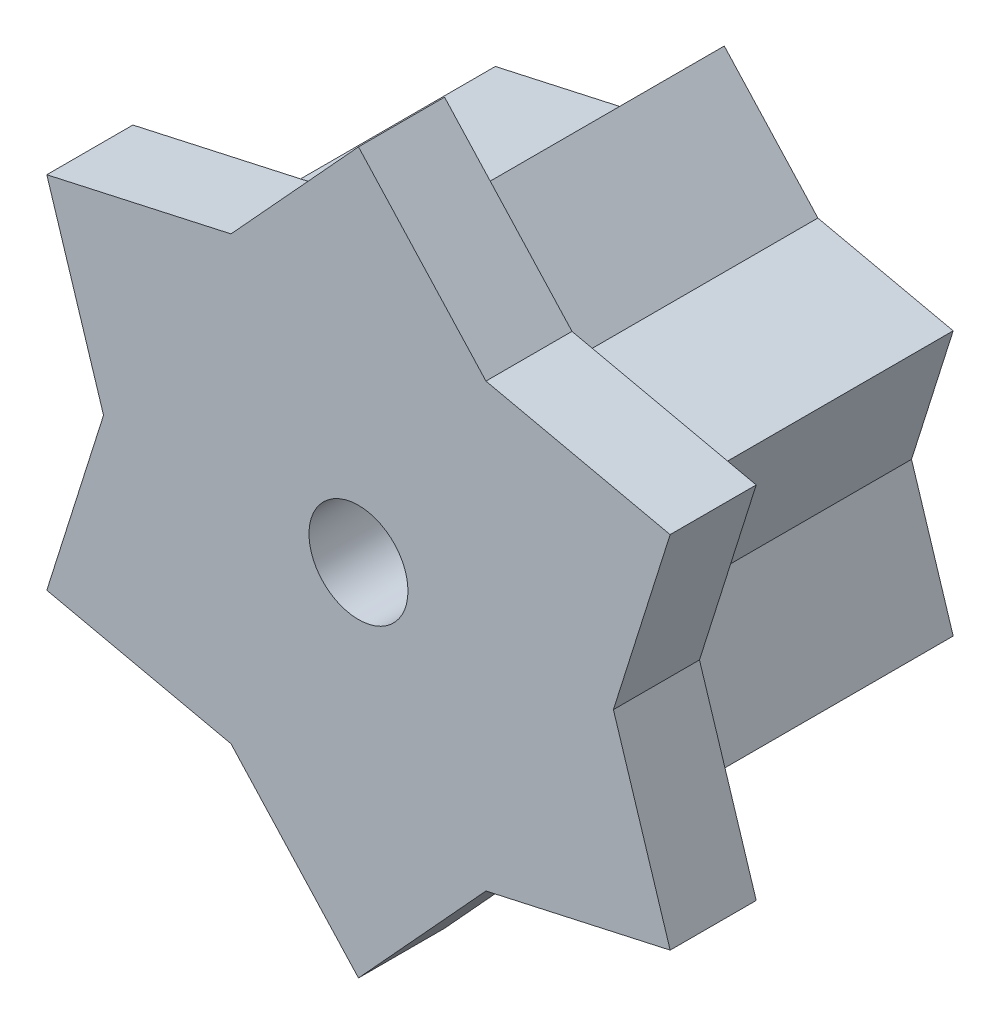
SolidWorks part; units mm, degrees
ref_plane "Front Plane" through (0, 0, 0) normal (0, 0, 1) x (1, 0, 0)
ref_plane "Top Plane" through (0, 0, 0) normal (0, 1, 0) x (1, 0, 0)
ref_plane "Right Plane" through (0, 0, 0) normal (1, 0, 0) x (0, 0, -1)
sketch "Sketch1" plane through (0, 0, 0) normal (0, 0, 1) x (1, 0, 0)
  line L0 (0, 6.1428) -> (0, -5.749) construction
  line L1 (-3.0597, 2.8037) -> (0, 6.1428)
  line L2 (0, 6.1428) -> (3.0597, 2.8037)
  line L3 (0.8982, 4.0516) -> (5.3198, 3.0714)
  line L4 (5.3198, 3.0714) -> (3.9579, -1.2479)
  line L5 (3.9579, 1.2479) -> (5.3198, -3.0714)
  line L6 (5.3198, -3.0714) -> (0.8982, -4.0516)
  line L7 (3.0597, -2.8037) -> (0, -6.1428)
  line L8 (0, -6.1428) -> (-3.0597, -2.8037)
  line L9 (-0.8982, -4.0516) -> (-5.3198, -3.0714)
  line L10 (-5.3198, -3.0714) -> (-3.9579, 1.2479)
  line L11 (-3.9579, -1.2479) -> (-5.3198, 3.0714)
  line L12 (-5.3198, 3.0714) -> (-0.8982, 4.0516)
  circle A0 centre (0, 0) radius 1.15
  circle A1 centre (0, 0) radius 4.15
  point P26 (0, 0)
  dimension "D1" = 2.3
  dimension "D3" = 85
  dimension "D4" = 42.5
  dimension "D2" = 3
  dimension "D5" = 6
extrude "Boss-Extrude1" add sketch "Sketch1" against normal blind 6.5 contours A1 A0 | A1 L1 L12 L11 L10 | L2 L0 A1 L3 | L0 L1 L12 A1 | A1 L12 L1 | A1 L2 L3 | A1 L5 L4 L3 L2 | L0 A1 A0 | A1 L11 L10 L9 L8 | A1 L10 L11 | A1 L8 L9 | A1 L9 L8 L7 L6 | A1 L6 L7 | A1 L7 L6 L5 L4 | A1 L4 L5 | A0 L0 | L0 A0 region at (0.718, 4.7126, 0) region at (-0.718, 4.7126, 0) region at (1.8672, 0, 0) region at (-1.8672, 0, 0) region at (-2.0957, 3.6299, 0) region at (-4.0813, 2.3563, 0) region at (4.0813, 2.3563, 0) region at (2.0957, 3.6299, 0) region at (0.4881, 0, 0) region at (-0.4881, 0, 0) region at (-4.1915, 0, 0) region at (-4.0813, -2.3563, 0) region at (4.1915, 0, 0) region at (4.0813, -2.3563, 0) region at (0.4572, -4.1746, 0) region at (-2.0957, -3.6299, 0) region at (2.0957, -3.6299, 0)
sketch "Sketch2" plane through (0, 0, 0) normal (0, 0, 1) x (1, 0, 0)
  line L0 (2.9621, 5.1305) -> (0, 8.3631)
  line L1 (0, 8.3631) -> (-2.9621, 5.1305)
  line L2 (-2.9621, 5.1305) -> (-7.2426, 4.1815)
  line L3 (-7.2426, 4.1815) -> (-5.9242, 0)
  line L4 (-5.9242, 0) -> (-7.2426, -4.1815)
  line L5 (-7.2426, -4.1815) -> (-2.9621, -5.1305)
  line L6 (-2.9621, -5.1305) -> (0, -8.3631)
  line L7 (0, -8.3631) -> (2.9621, -5.1305)
  line L8 (2.9621, -5.1305) -> (7.2426, -4.1815)
  line L9 (7.2426, -4.1815) -> (5.9242, 0)
  line L10 (5.9242, 0) -> (7.2426, 4.1815)
  line L11 (7.2426, 4.1815) -> (2.9621, 5.1305)
  line L12 (5.3198, -3.0714) -> (4.3514, 0)
  line L13 (4.3514, 0) -> (5.3198, 3.0714)
  line L14 (5.3198, 3.0714) -> (2.1757, 3.7684)
  line L15 (2.1757, 3.7684) -> (0, 6.1428)
  line L16 (0, 6.1428) -> (-2.1757, 3.7684)
  line L17 (-2.1757, 3.7684) -> (-5.3198, 3.0714)
  line L18 (-5.3198, 3.0714) -> (-4.3514, 0)
  line L19 (-4.3514, 0) -> (-5.3198, -3.0714)
  line L20 (-5.3198, -3.0714) -> (-2.1757, -3.7684)
  line L21 (-2.1757, -3.7684) -> (0, -6.1428)
  line L22 (0, -6.1428) -> (2.1757, -3.7684)
  line L23 (2.1757, -3.7684) -> (5.3198, -3.0714)
  line L24 (5.3198, -3.0714) -> (4.3514, 0)
  line L25 (4.3514, 0) -> (5.3198, 3.0714)
  line L26 (5.3198, 3.0714) -> (2.1757, 3.7684)
  line L27 (2.1757, 3.7684) -> (0, 6.1428)
  line L28 (0, 6.1428) -> (-2.1757, 3.7684)
  line L29 (-2.1757, 3.7684) -> (-5.3198, 3.0714)
  line L30 (-5.3198, 3.0714) -> (-4.3514, 0)
  line L31 (-4.3514, 0) -> (-5.3198, -3.0714)
  line L32 (-5.3198, -3.0714) -> (-2.1757, -3.7684)
  line L33 (-2.1757, -3.7684) -> (0, -6.1428)
  line L34 (0, -6.1428) -> (2.1757, -3.7684)
  line L35 (2.1757, -3.7684) -> (5.3198, -3.0714)
  line M25 (5.3198, -3.0714) -> (4.3514, 0)
  line M26 (4.3514, 0) -> (5.3198, 3.0714)
  line M27 (5.3198, 3.0714) -> (2.1757, 3.7684)
  line M28 (2.1757, 3.7684) -> (0, 6.1428)
  line M29 (0, 6.1428) -> (-2.1757, 3.7684)
  line M30 (-2.1757, 3.7684) -> (-5.3198, 3.0714)
  line M31 (-5.3198, 3.0714) -> (-4.3514, 0)
  line M32 (-4.3514, 0) -> (-5.3198, -3.0714)
  line M33 (-5.3198, -3.0714) -> (-2.1757, -3.7684)
  line M34 (-2.1757, -3.7684) -> (0, -6.1428)
  line M35 (0, -6.1428) -> (2.1757, -3.7684)
  line M36 (2.1757, -3.7684) -> (5.3198, -3.0714)
  dimension "D1" = 0
  dimension "D2" = 1.5
extrude "Boss-Extrude2" add sketch "Sketch2" along normal blind 2 contours M36 M25 M26 M27 M28 M29 M30 M31 M32 M33 M34 M35 | L10 L11 L0 L1 L2 L3 L4 L5 L6 L7 L8 L9 M25 M36 M35 M34 M33 M32 M31 M30 M29 M28 M27 M26 region at (5.0545, 4.44, 0) region at (0, 0, 0)
extrude "Cut-Extrude1" cut sketch "Sketch1<4>" against normal through all both and the other way through all contours A0 L0 | L0 A0 region at (0.4881, 0, 0) region at (-0.4881, 0, 0)
sketch "Sketch1<4>" plane through (0, 0, 0) normal (0, 0, 1) x (1, 0, 0) same geometry as "Sketch1"
sketch "Sketch3" [suppressed] plane through (0, 0, 2) normal (0, 0, 1) x (1, 0, 0)
  line L0 (0, 0) -> (-12.6109, 0) construction
  line L1 (0.6538, 1.35) -> (-0.6538, 1.35)
  circle A0 centre (0, 0) radius 1.5
  dimension "D1" = 3.2
  dimension "D2" = 2.9
extrude "Cut-Extrude2" [suppressed] cut sketch "Sketch3" against normal through all contours L0 A0 L1 | A0 L0
chamfer "Chamfer1" distance 0.4 angle 45 12 edges at (3.7477, -3.4199, 0) (1.0878, -4.9556, 0) (-1.0878, -4.9556, 0) (-3.7477, -3.4199, 0) (-4.8356, -1.5357, 0) (-4.8356, 1.5357, 0) (-3.7477, 3.4199, 0) (4.8356, -1.5357, 0) (4.8356, 1.5357, 0) (3.7477, 3.4199, 0) (1.0878, 4.9556, 0) (-1.0878, 4.9556, 0)
